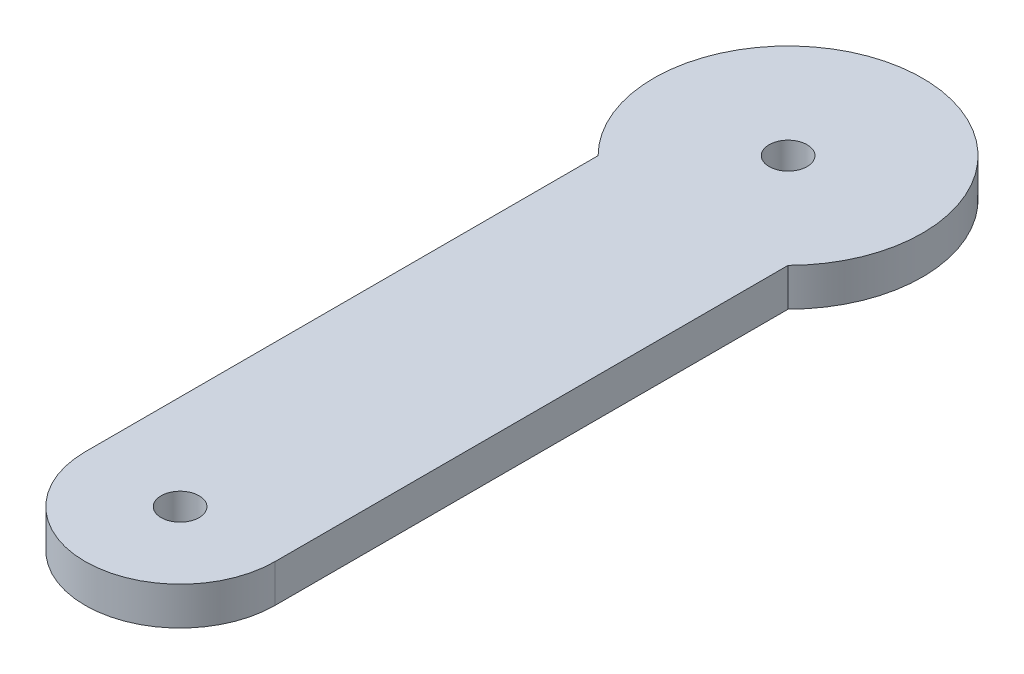
SolidWorks part; units mm, degrees
ref_plane "Front Plane" through (0, 0, 0) normal (0, 0, 1) x (1, 0, 0)
ref_plane "Top Plane" through (0, 0, 0) normal (0, 1, 0) x (1, 0, 0)
ref_plane "Right Plane" through (0, 0, 0) normal (1, 0, 0) x (0, 0, -1)
sketch "Sketch1" plane through (0, 0, 0) normal (0, 1, 0) x (1, 0, 0)
  line L0 (0, 0) -> (0, 80) construction
  line L1 (0, 80) -> (-12.5, 67.5) construction
  line L2 (-12.5, 67.5) -> (12.5, 67.5) construction
  line L3 (12.5, 67.5) -> (0, 80) construction
  line L4 (-12.5, 67.5) -> (-12.5, 0)
  line L5 (12.5, 67.5) -> (12.5, 0)
  arc A0 (12.5, 67.5) -> (-12.5, 67.5) centre (0, 80) ccw
  arc A1 (12.5, 0) -> (-12.5, 0) centre (0, 0) cw
  circle A2 centre (0, 0) radius 2.5
  circle A3 centre (0, 0) radius 20 construction
  circle A4 centre (0, 30) radius 10 construction
  circle A5 centre (0, 80) radius 2.5
  point P12 (0, 10.11)
  dimension "D2" = 25
  dimension "D3" = 5
  dimension "D4" = 40
  dimension "D5" = 20
  dimension "D6" = 30
  dimension "D7" = 5
  dimension "D1" = 80
other "AlignGroup1"
extrude "Boss-Extrude1" add sketch "Sketch1" along normal blind 5
